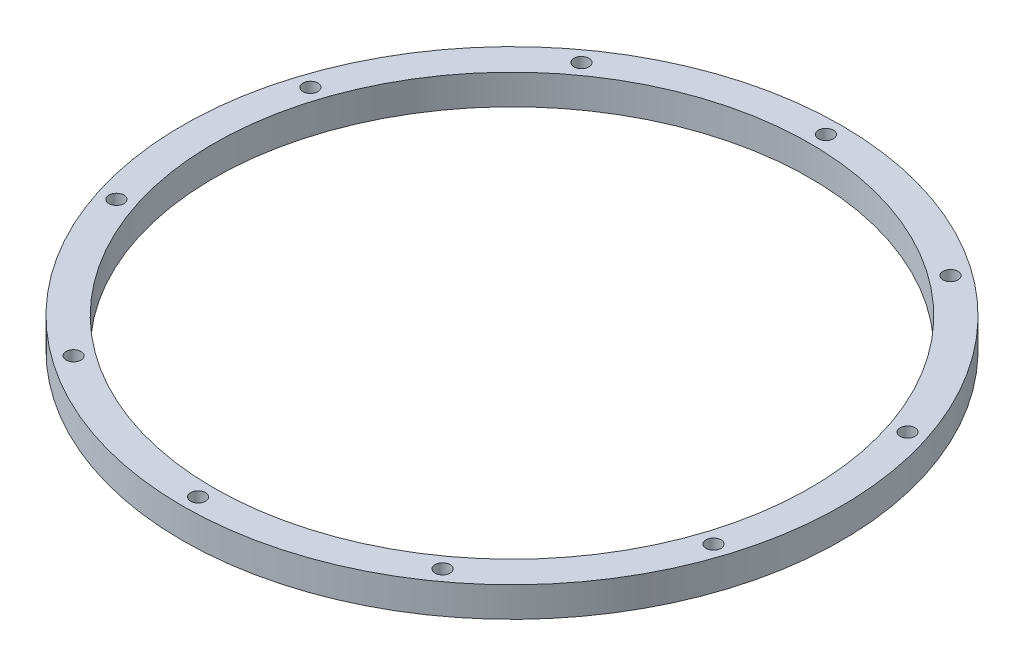
SolidWorks part; units mm, degrees
note: The reader was unsure of these and kept them because the rebuilt part matched: shared geometry of "Эскиз1<5>".
material "Простая углеродистая сталь"
ref_plane "Спереди" through (0, 0, 0) normal (0, 0, 1) x (1, 0, 0)
ref_plane "Сверху" through (0, 0, 0) normal (0, 1, 0) x (1, 0, 0)
ref_plane "Справа" through (0, 0, 0) normal (1, 0, 0) x (0, 0, -1)
sketch "Эскиз1" plane through (0, 0, 0) normal (0, 1, 0) x (1, 0, 0)
  circle A0 centre (0, 0) radius 246.95
  circle A1 centre (0, 0) radius 223.5
  circle A2 centre (0, 0) radius 223.225
  circle A3 centre (0, 0) radius 235.225 construction
  circle A4 centre (0, -235.225) radius 5.6125
extrude "Бобышка-Вытянуть5" add sketch "Эскиз1" along normal blind 22.45 contours A0 | A1
sketch "Эскиз4" plane through (0, 22.45, 0) normal (0, 1, 0) x (1, 0, 0)
extrude "Вырез-Вытянуть1" cut sketch "Эскиз1<5>" along normal through all contours A4
sketch "Эскиз1<5>" plane through (0, 0, 0) normal (0, 1, 0) x (1, 0, 0) same geometry as "Эскиз1"
pattern_circular "Круговой массив2" count 10 over 360 about axis through (0, 0, 0) along (0, 1, 0) of "Вырез-Вытянуть1"
